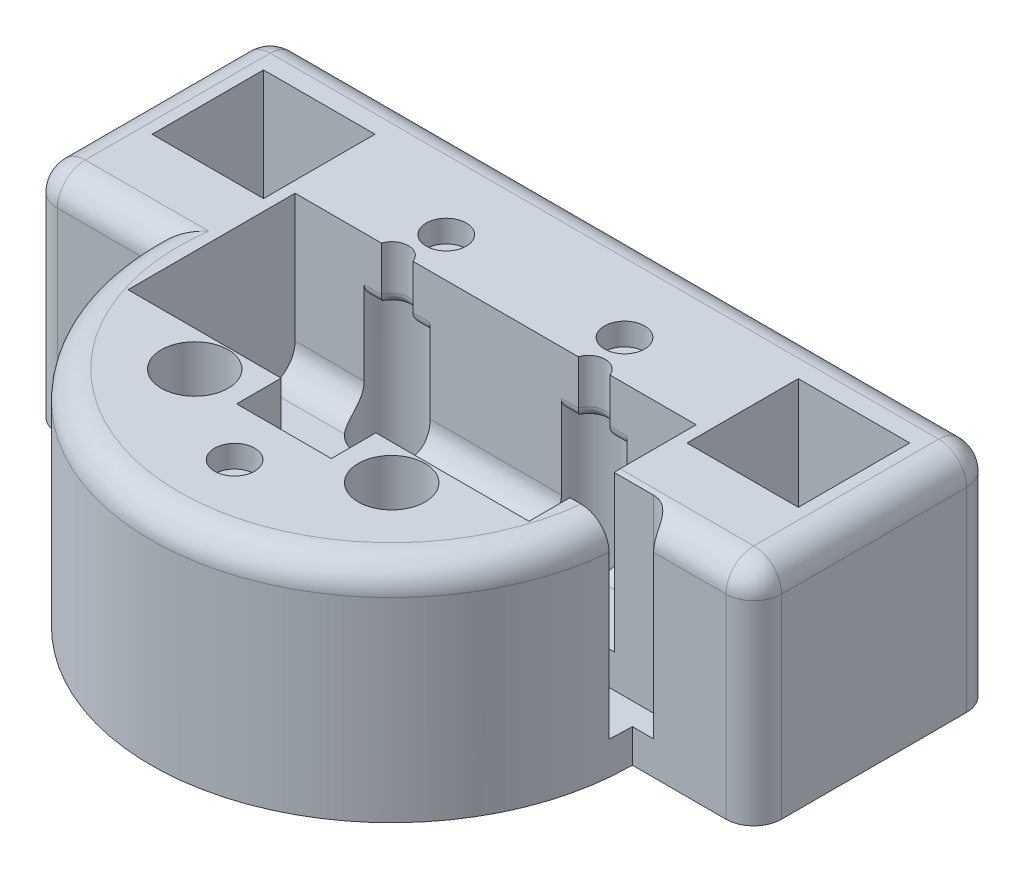
SolidWorks part; units mm, degrees
ref_plane "Front Plane" through (0, 0, 0) normal (0, 0, 1) x (1, 0, 0)
ref_plane "Top Plane" through (0, 0, 0) normal (0, 1, 0) x (1, 0, 0)
ref_plane "Right Plane" through (0, 0, 0) normal (1, 0, 0) x (0, 0, -1)
sketch "Sketch1" plane through (0, 0, 0) normal (0, 1, 0) x (1, 0, 0)
  line L0 (-65, 43.2) -> (65, 43.2)
  line L1 (43.2, 0) -> (65, 0)
  line L2 (65, 0) -> (65, 43.2)
  line L3 (-43.2, 0) -> (-65, 0)
  line L4 (-65, 0) -> (-65, 43.2)
  circle A0 centre (0, 0) radius 25 construction
  circle A1 centre (0, 0) radius 43.2
  point P6 (0, 43.2)
  dimension "D1" = 86.4
  dimension "D2" = 50
  dimension "D3" = 130
extrude "Boss-Extrude1" add sketch "Sketch1" along normal blind 40 contours A1 | A1 L0 L4 L3 | A1 L1 L2 L0 region at (-47.9685, 0, -25.1658) region at (47.9685, 0, -25.1658) region at (0, 0, 0)
sketch "Sketch2" plane through (0, 40, 0) normal (0, 1, 0) x (1, 0, 0)
  line L0 (65, 25) -> (48, 25) construction
  line L1 (65, 0) -> (65, 43.2) construction
  line L2 (48, 25) -> (48, 43.2) construction
  line L3 (-65, 43.2) -> (65, 43.2) construction
  line L4 (-65, 25) -> (-48, 25) construction
  line L6 (-48, 25) -> (-48, 43.2) construction
  line L8 (38, 15) -> (58, 15)
  line L9 (38, 15) -> (38, 35)
  line L10 (38, 35) -> (58, 35)
  line L11 (58, 15) -> (58, 35)
  line L12 (38, 15) -> (58, 35) construction
  line L13 (38, 35) -> (58, 15) construction
  line L14 (-58, 15) -> (-38, 15)
  line L15 (-58, 15) -> (-58, 35)
  line L16 (-58, 35) -> (-38, 35)
  line L17 (-38, 15) -> (-38, 35)
  line L18 (-58, 15) -> (-38, 35) construction
  line L19 (-58, 35) -> (-38, 15) construction
  circle A0 centre (0, 0) radius 25 construction
  circle A10 centre (0, 0) radius 25 construction
  circle A12 centre (0, 0) radius 25 construction
  circle A14 centre (0, 0) radius 25 construction
  circle A16 centre (0, 0) radius 25 construction
  circle A18 centre (0, 0) radius 25 construction
  circle A20 centre (0, 0) radius 25 construction
  circle A22 centre (0, 0) radius 25 construction
  circle A31 centre (17.6777, 17.6777) radius 3
  circle A33 centre (17.6777, -17.6777) radius 3
  circle A35 centre (-17.6777, -17.6777) radius 3
  circle A37 centre (-17.6777, 17.6777) radius 3
  point P21 (0, -12.5)
  point P30 (0, 0)
  point P68 (0, 0)
  dimension "D1" = 8
  dimension "D2" = 50
  dimension "D8" = 6
  dimension "D4" = 17
  dimension "D5" = 20
  dimension "D6" = 20
extrude "Cut-Extrude1" cut sketch "Sketch2" against normal blind 50
sketch "Sketch3" plane through (0, 40, 0) normal (0, 1, 0) x (1, 0, 0)
  line L0 (0, -11.3388) -> (0, -19.3388)
  line L1 (-36, -11.3388) -> (36, -11.3388)
  line L2 (-36, -11.3388) -> (-36, 18.6612)
  line L3 (-36, 18.6612) -> (36, 18.6612)
  line L4 (36, -11.3388) -> (36, 18.6612)
  line L5 (-36, 3.6612) -> (36, 3.6612) construction
  line L6 (0, 3.6612) -> (0, -43.2) construction
  line L7 (0, -19.3388) -> (8.5, -19.3388)
  line L8 (8.5, -19.3388) -> (8.5, -11.3388)
  line L9 (0, -19.3388) -> (-8.5, -19.3388)
  line L10 (-8.5, -19.3388) -> (-8.5, -11.3388)
  line L11 (0, 25) -> (0, 18.6612) construction
  line L12 (17.6777, -17.6777) -> (17.6777, -11.3388) construction
  circle A1 centre (0, 0) radius 43.2 construction
  dimension "D1" = 8
  dimension "D2" = 8.5
  dimension "D3" = 72
  dimension "D4" = 30
  dimension "D5" = 6.3388
extrude "Cut-Extrude2" cut sketch "Sketch3" against normal blind 28 contours L7 L8 L1 L0 | L10 L9 L0 L1 | L1 L4 L3 L2 region at (4.25, 40, 15.3388) region at (-4.25, 40, 15.3388) region at (0, 40, -3.6612)
fillet "Fillet1" radius 5 4 edges at (-28.2559, 12, -18.6612) (28.2559, 12, -18.6612) (22.25, 12, 11.3388) (-22.25, 12, 11.3388)
sketch "Sketch4" plane through (0, 40, 0) normal (0, 1, 0) x (1, 0, 0)
  line L3 (23.0144, 4) -> (43.0144, 4)
  line L4 (23.0144, -4) -> (43.0144, -4)
  circle A1 centre (23.0144, 0) radius 4
  circle A2 centre (0, 0) radius 43.2 construction
  arc A3 (43.0144, 4) -> (43.0144, -4) centre (43.0144, 0) cw
  dimension "D1" = 8
  dimension "D2" = 20
extrude "Cut-Extrude3" cut sketch "Sketch4" against normal blind 34 contours L4 L3 | A1 L4 L3 | A1 | A3 region at (36.156, 40, 0) region at (23.0144, 40, 0)
sketch "Sketch5" plane through (0, 40, 0) normal (0, 1, 0) x (1, 0, 0)
  line L0 (-36, -12.2) -> (-36, -20.2) construction
  line L1 (-36, -20.2) -> (36, -20.2) construction
  line L2 (36, -20.2) -> (36, -12.2) construction
  line L3 (-36, -12.2) -> (36, -12.2) construction
  line L4 (-36, 17.8) -> (-36, 25.8) construction
  line L5 (-36, 25.8) -> (36, 25.8) construction
  line L6 (36, 25.8) -> (36, 17.8) construction
  line L7 (36, 17.8) -> (-36, 17.8) construction
  line L8 (-16, 25.8) -> (-16, 17.8) construction
  line L9 (16, 25.8) -> (16, 17.8) construction
  line L10 (-16, -12.2) -> (-16, -20.2) construction
  line L11 (16, -12.2) -> (16, -20.2) construction
  line L12 (36, 17.8) -> (36, -12.2) construction
  line L13 (0, -12.2) -> (0, -43.2) construction
  line L14 (-8.5, -28.2) -> (8.5, -28.2) construction
  circle A2 centre (16, 25.8) radius 3.6
  circle A3 centre (-16, 25.8) radius 3.6
  arc A4 (43.0144, 4) -> (43.0144, -4) centre (0, 0) ccw construction
  circle A5 centre (0, -28.2) radius 3.6
  dimension "D7" = 7.2
  dimension "D8" = 8
  dimension "D1" = 8
  dimension "D2" = 8
  dimension "D3" = 20
  dimension "D4" = 20
  dimension "D5" = 20
  dimension "D6" = 20
extrude "Cut-Extrude4" cut sketch "Sketch5" against normal blind 4
fillet "Fillet3" radius 5 10 edges at (-2.0022, 40, 43.1536) (56.0072, 40, 0) (-54.1, 40, 0) (-65, 40, -21.6) (65, 40, -21.6) (0, 40, -43.2) (65, 20, 0) (65, 20, -43.2) (-65, 20, -43.2) (-65, 20, 0)
sketch "Sketch7" plane through (0, 40, 0) normal (0, 1, 0) x (1, 0, 0)
  line L1 (8.5, -11.3388) -> (36, -11.3388) construction
  circle A1 centre (17.6777, -17.6777) radius 6
  circle A2 centre (-17.6777, -17.6777) radius 6
  dimension "D1" = 12
  dimension "D3" = 6.3388
extrude "Cut-Extrude5" cut sketch "Sketch7" against normal blind 36 from offset 0
sketch "Sketch8" plane through (0, 40, 0) normal (0, 1, 0) x (1, 0, 0)
  circle A0 centre (-17.6777, 17.6777) radius 6
  circle A1 centre (17.6777, 17.6777) radius 5.9532
  dimension "D1" = 12
extrude "Cut-Extrude6" cut sketch "Sketch8" against normal blind 26 from offset 10 offset against normal yes
fillet "Fillet4" radius 2 6 edges at (22.0305, 30, -18.6612) (13.3249, 30, -18.6612) (17.6777, 30, -20.6777) (-22.0542, 30, -18.6612) (-13.3011, 30, -18.6612) (-17.6777, 30, -20.6777)
